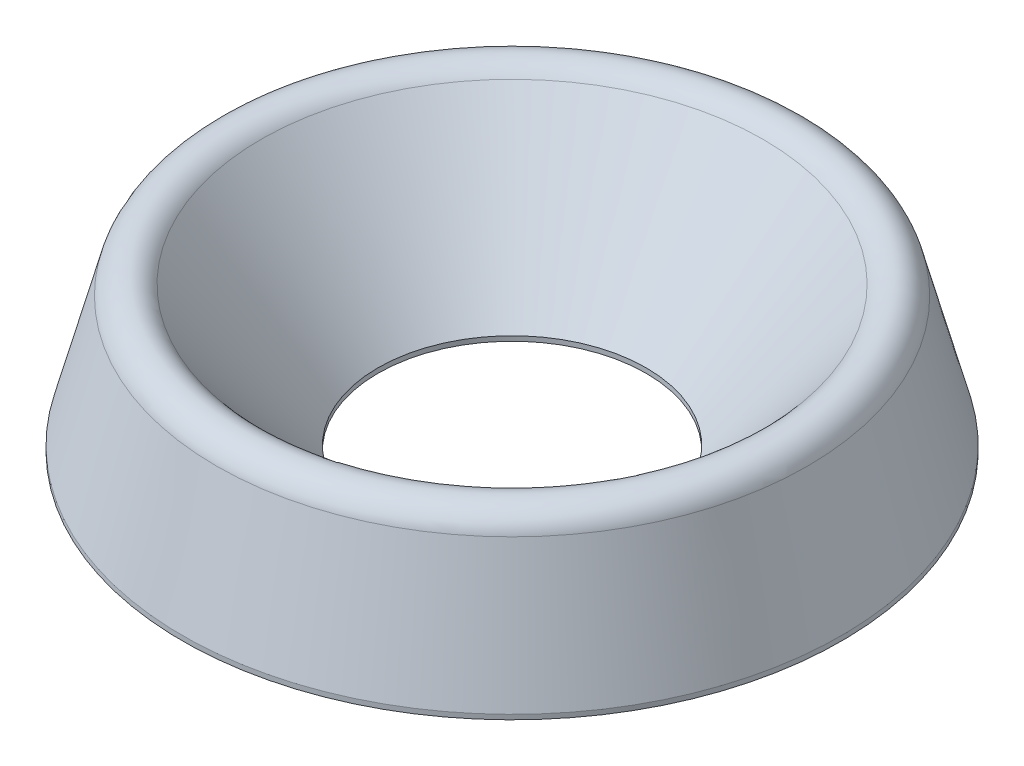
SolidWorks part; units mm, degrees
ref_plane "Front Plane" through (0, 0, 0) normal (0, 0, 1) x (1, 0, 0)
ref_plane "Top Plane" through (0, 0, 0) normal (0, 1, 0) x (1, 0, 0)
ref_plane "Right Plane" through (0, 0, 0) normal (1, 0, 0) x (0, 0, -1)
sketch "Sketch1" plane through (0, 0, 0) normal (0, 0, 1) x (1, 0, 0)
  line L0 (0, 0) -> (0, 3.4451) construction
  line L1 (-3.556, 0) -> (-3.556, 3.4451) construction
  line L2 (-8.7376, 0) -> (-8.7376, 0.127)
  line L3 (-8.7376, 0) -> (-8.7376, 3.4451) construction
  line L4 (-3.556, 0.127) -> (-6.6565, 3.822)
  line L5 (-3.556, 0.127) -> (-3.556, 0)
  line L6 (-3.556, 0) -> (-8.7376, 0)
  line L7 (-8.7376, 0) -> (-3.556, 0) construction
  line L8 (-7.1754, 0) -> (-7.1754, 3.4451) construction
  line L9 (-8.7376, 0.127) -> (-7.8302, 3.5598)
  arc A0 (-7.8302, 3.5598) -> (-6.6565, 3.822) centre (-7.1754, 3.3867) cw
  arc A1 (7.8302, 3.5598) -> (6.6565, 3.822) centre (7.1754, 3.3867) ccw construction
  dimension "D1" = 0.127
  dimension "D2" = 40
  dimension "D3" = 0.6773
  dimension "ID" = 7.112
  dimension "OD" = 17.4752
  dimension "Height" = 4.064
revolve "Revolve1" add sketch "Sketch1" angle 360 about L0
shell "Shell2" thickness 0.7937 removed face at (0, 0, -3.556)
equation "\"D3@Sketch1\" = \"Height@Sketch1\"/6"
